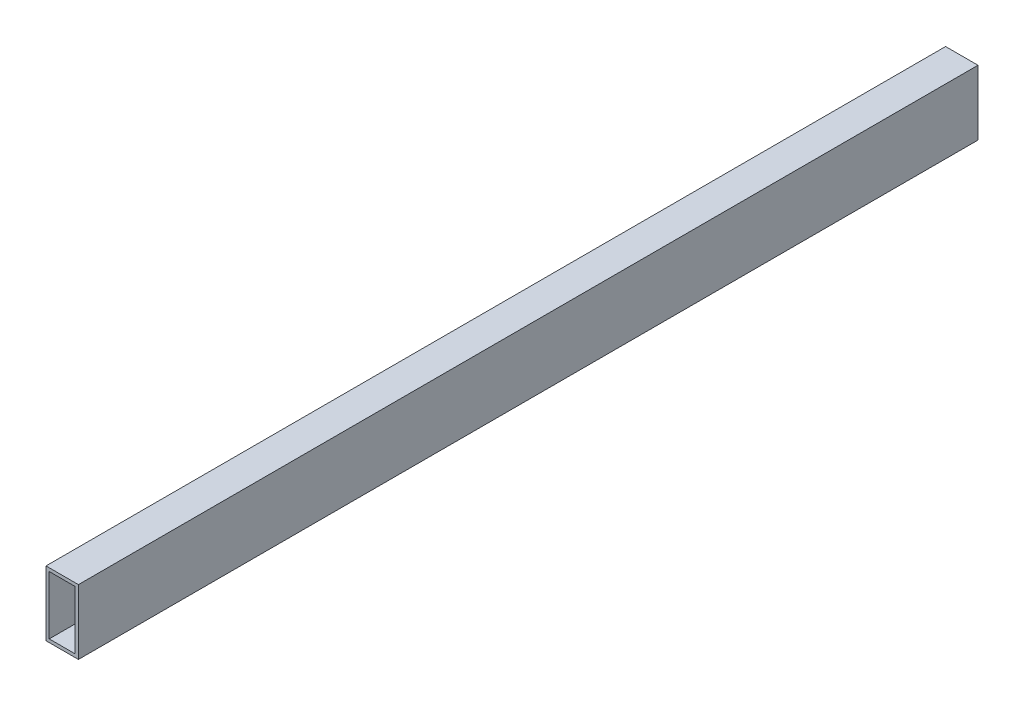
SolidWorks part; units mm, degrees
material "6061-T6 (SS)"
ref_plane "Front" through (0, 0, 0) normal (0, 0, 1) x (1, 0, 0)
ref_plane "Top" through (0, 0, 0) normal (0, 1, 0) x (1, 0, 0)
ref_plane "Right" through (0, 0, 0) normal (1, 0, 0) x (0, 0, -1)
sketch "Sketch1" plane through (0, 0, 0) normal (0, 0, 1) x (1, 0, 0)
  line L1 (-12.7, -25.4) -> (12.7, -25.4)
  line L2 (-12.7, -25.4) -> (-12.7, 25.4)
  line L3 (-12.7, 25.4) -> (12.7, 25.4)
  line L4 (12.7, -25.4) -> (12.7, 25.4)
  line L5 (-12.7, -25.4) -> (12.7, 25.4) construction
  line L6 (-12.7, 25.4) -> (12.7, -25.4) construction
  point P0 (0, 0)
  dimension "D1" = 50.8
  dimension "D2" = 25.4
extrude "Extrude-Thin1" add sketch "Sketch1" along normal blind 704.85 thin thin type one direction reverse wall 2.54
